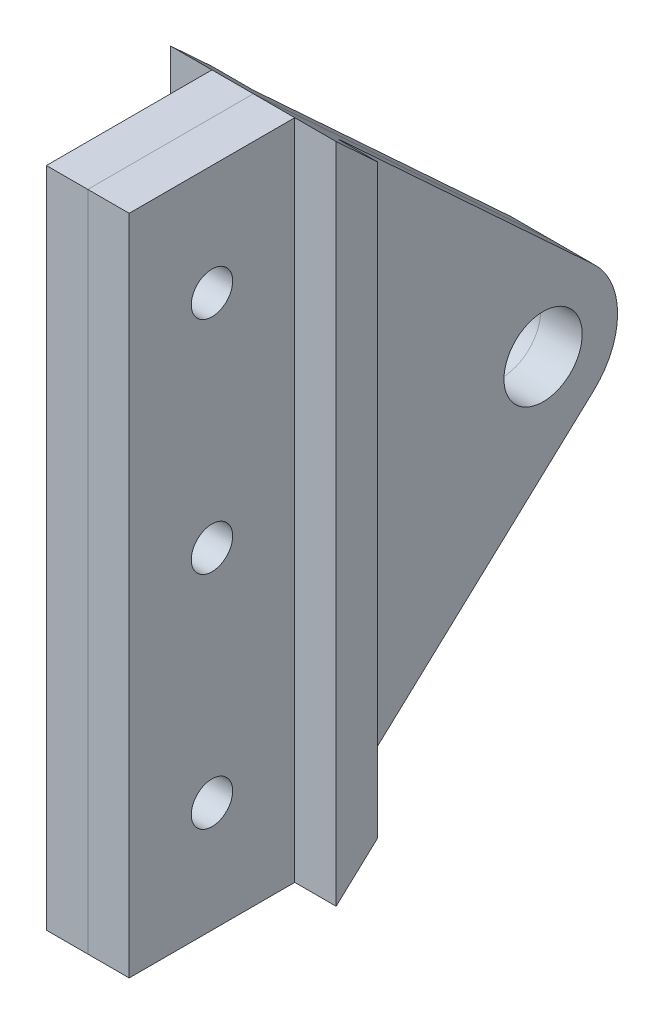
SolidWorks part; units mm, degrees
ref_plane "Front Plane" through (0, 0, 0) normal (0, 0, 1) x (1, 0, 0)
ref_plane "Top Plane" through (0, 0, 0) normal (0, 1, 0) x (1, 0, 0)
ref_plane "Right Plane" through (0, 0, 0) normal (1, 0, 0) x (0, 0, -1)
sketch "Sketch1" plane through (0, 0, 0) normal (1, 0, 0) x (0, 0, -1)
  line L0 (1402.1376, 104.8883) -> (1356.2774, 147.2964)
  line L1 (1330.8774, 96.4964) -> (1475.9878, 96.4964) construction
  line L2 (1356.2774, 147.2964) -> (1330.8774, 147.2964)
  line L3 (1356.2774, 147.2964) -> (1356.2774, 45.6964) construction
  line L4 (1330.8774, 147.2964) -> (1330.8774, 45.6964)
  line L5 (1330.8774, 45.6964) -> (1356.2774, 45.6964)
  line L6 (1356.2774, 45.6964) -> (1402.1376, 88.1045)
  line L7 (1343.5774, 147.2964) -> (1343.5774, 45.6964) construction
  line L8 (1356.2774, 147.2964) -> (1356.2774, 45.6964)
  line L9 (1362.6274, 141.4244) -> (1362.6274, 51.5684)
  line L13 (1389.1542, 85.1404) -> (1398.6936, 80.7531)
  line L14 (1398.6936, 80.7531) -> (1409.14, 103.4651)
  line L15 (1409.14, 103.4651) -> (1399.6006, 107.8524)
  circle A0 centre (1394.3774, 96.4964) radius 11.43
  circle A1 centre (1343.5774, 96.4964) radius 3.175
  circle A2 centre (1343.5774, 130.3631) radius 3.175
  circle A3 centre (1343.5774, 62.6298) radius 3.175
  ellipse E2 centre (1394.3774, 96.4964) end of major axis (1406.8774, 96.4964) minor radius 12.4995 (1399.6006, 107.8524) -> (1389.1542, 85.1404) ccw
  ellipse E3 centre (1394.3774, 96.4964) end of major axis (1388.3774, 96.4964) minor radius 5.9998
  point P9 (1343.5774, 96.4964)
  dimension "D1" = 22.86
  dimension "D5" = 6.35
  dimension "D2" = 101.6
  dimension "D3" = 25.4
  dimension "D4" = 38.1
  dimension "D6" = 33.8667
  dimension "D7" = 31.75
extrude "Boss-Extrude1" add sketch "Sketch1" along normal blind 6.35 contours E2 L0 L9 L6 L13 | L0 E2 L13 L6 L14 A0 | A0 L14 E3 | L14 A0 | A0 L14 L6 | L9 L0 L8 L6 | L8 L2 L4 L5 A1 A2 A3 region at (0, 96.4964, -1359.3875) region at (0, 96.5505, -1374.0719) region at (0, 96.4964, -1355.2302) region at (0, 106.581, -1400.2576) region at (0, 100.9465, -1404.5537) region at (0, 88.0296, -1402.0562) region at (0, 91.9528, -1404.2559)
extrude "Boss-Extrude2" add sketch "Sketch1<4>" along normal blind 12.7 contours L9 L0 L8 L6 region at (0, 96.4964, -1359.3875)
sketch "Sketch1<4>" plane through (0, 0, 0) normal (1, 0, 0) x (0, 0, -1) same geometry as "Sketch1"
mirror "Mirror1" about plane through (0, 0, 0) normal (1, 0, 0) of bodies 104
